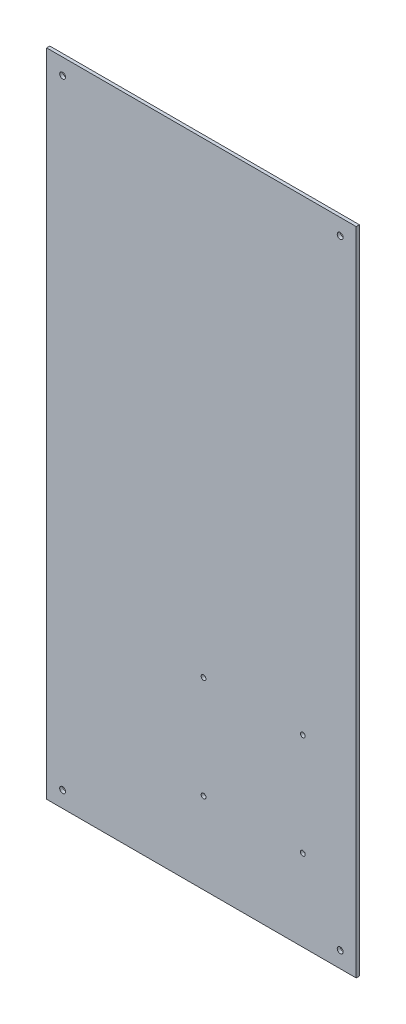
SolidWorks part; units mm, degrees
material "Acrylic (Medium-high impact)"
ref_plane "Front Plane" through (0, 0, 0) normal (0, 0, 1) x (1, 0, 0)
ref_plane "Top Plane" through (0, 0, 0) normal (0, 1, 0) x (1, 0, 0)
ref_plane "Right Plane" through (0, 0, 0) normal (1, 0, 0) x (0, 0, -1)
sketch "Sketch1" plane through (0, 0, 0) normal (0, 0, 1) x (1, 0, 0)
  line L0 (159.5, 0) -> (-159.5, 0) construction
  line L1 (-145, 304.8) -> (145, 304.8)
  line L2 (-145, 304.8) -> (-145, -304.8)
  line L3 (-145, -304.8) -> (145, -304.8)
  line L4 (145, 304.8) -> (145, -304.8)
  line L5 (-145, 304.8) -> (145, -304.8) construction
  line L6 (-145, -304.8) -> (145, 304.8) construction
  point P0 (0, 0)
  point P5 (-129.995, 289.795)
  point P6 (129.995, 289.795)
  point P7 (2, -228.6)
  point P9 (2, -132.6)
  point P10 (95, -132.6)
  point P11 (95, -228.6)
  point P16 (129.995, -289.795)
  point P17 (-129.995, -289.795)
  dimension "D1" = 609.6
  dimension "D2" = 290
  dimension "D3" = 15.005
  dimension "D4" = 15.005
  dimension "D5" = 15.005
  dimension "D6" = 96
  dimension "D7" = 93
  dimension "D8" = 76.2
  dimension "D9" = 50
extrude "Boss-Extrude1" add sketch "Sketch1" along normal blind 3
hole_wizard "M5 Clearance Hole1" positions "Sketch2" profile "Sketch3" hole size "M5" standard "ANSI Metric" end condition through all
sketch "Sketch2" plane through (0, 0, 3) normal (0, 0, 1) x (1, 0, 0)
  point P0 (129.995, 289.795)
  point P3 (-129.995, 289.795)
  point P6 (-129.995, -289.795)
  point P9 (129.995, -289.795)
sketch "Sketch3" plane through (129.995, 289.795, 3) normal (1, 0, 0) x (0, -1, 0)
  line L0 (0, 0) -> (0, 3)
  line L1 (0, 3) -> (2.75, 3)
  line L2 (2.75, 3) -> (2.75, 0)
  line L5 (2.75, 0) -> (0, 0)
  line L11 (0, -6.35) -> (0, 107.95) construction
  dimension "Thru Hole Dia." = 5.5
  dimension "Thru Hole Depth" = 3
hole_wizard "M4 Clearance Hole1" positions "Sketch4" profile "Sketch5" hole size "M4" standard "ANSI Metric" end condition up to next
sketch "Sketch4" plane through (0, 0, 3) normal (0, 0, 1) x (1, 0, 0)
  point P0 (95, -132.6)
  point P3 (2, -132.6)
  point P6 (2, -228.6)
  point P9 (95, -228.6)
sketch "Sketch5" plane through (95, -132.6, 3) normal (1, 0, 0) x (0, -1, 0)
  line L0 (0, 0) -> (0, 3)
  line L1 (0, 3) -> (2.25, 3)
  line L2 (2.25, 3) -> (2.25, 0)
  line L5 (2.25, 0) -> (0, 0)
  line L11 (0, -6.35) -> (0, 107.95) construction
  dimension "Thru Hole Dia." = 4.5
  dimension "Thru Hole Depth" = 3
